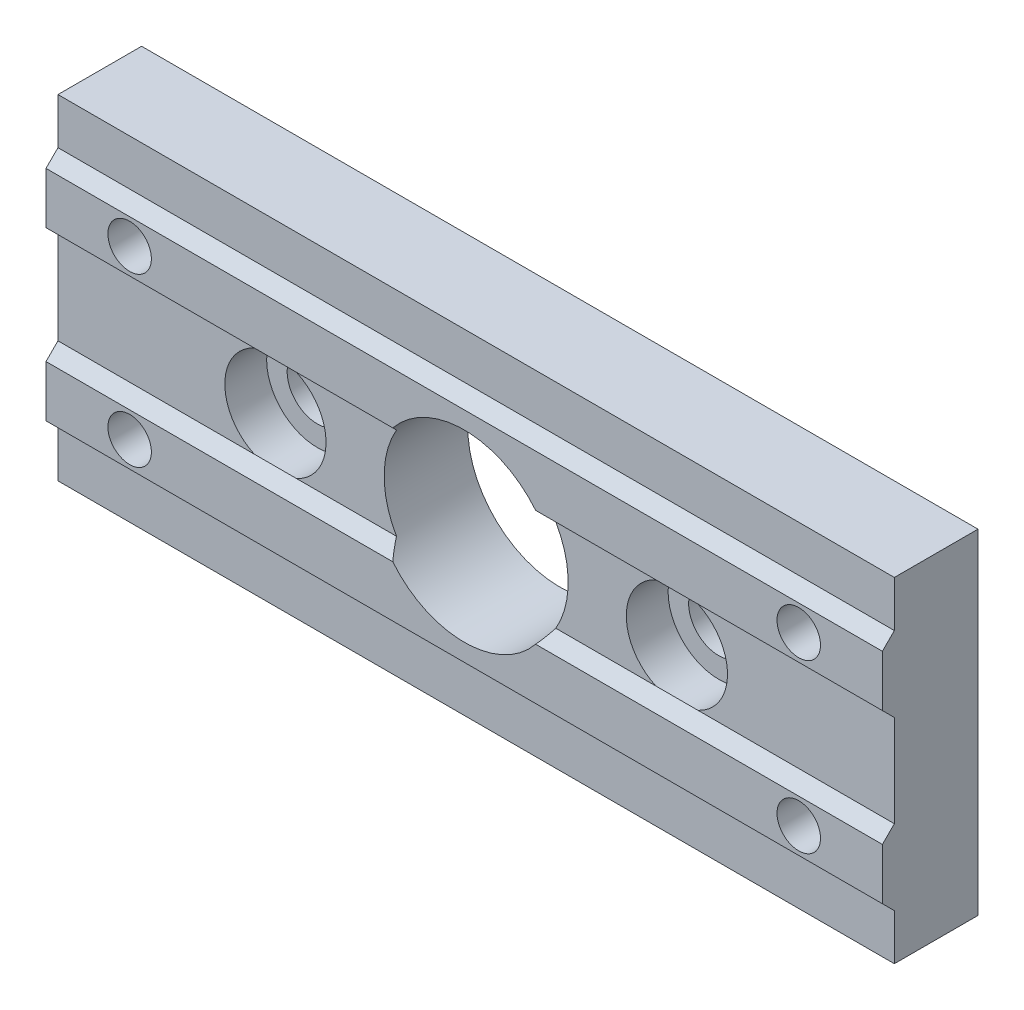
SolidWorks part; units mm, degrees
ref_plane "Płaszczyzna przednia" through (0, 0, 0) normal (0, 0, 1) x (1, 0, 0)
ref_plane "Płaszczyzna górna" through (0, 0, 0) normal (0, 1, 0) x (1, 0, 0)
ref_plane "Płaszczyzna prawa" through (0, 0, 0) normal (1, 0, 0) x (0, 0, -1)
sketch "Sketch1" plane through (0, 0, 0) normal (0, 0, 1) x (1, 0, 0)
  line L0 (-50, 10) -> (50, 10) construction
  line L1 (-50, -20) -> (50, -20)
  line L2 (-50, -20) -> (-50, 20)
  line L3 (-50, 20) -> (50, 20)
  line L4 (50, -20) -> (50, 20)
  line L5 (-50, -20) -> (50, 20) construction
  line L6 (-50, 20) -> (50, -20) construction
  line L7 (-50, -10) -> (50, -10) construction
  line L8 (-40, 20) -> (-40, -20) construction
  line L9 (40, 20) -> (40, -20) construction
  line L10 (-50, 0) -> (50, 0) construction
  circle A0 centre (0, 0) radius 11
  circle A1 centre (-40, 10) radius 2.6
  circle A2 centre (-40, -10) radius 2.6
  circle A3 centre (40, 10) radius 2.6
  circle A4 centre (40, -10) radius 2.6
  circle A5 centre (-24, 0) radius 3.6
  circle A6 centre (24, 0) radius 3.6
  point P0 (0, 0)
  dimension "D7" = 22
  dimension "D8" = 5.2
  dimension "D9" = 7.2
  dimension "D1" = 100
  dimension "D2" = 40
  dimension "D3" = 10
  dimension "D4" = 10
  dimension "D5" = 10
  dimension "D6" = 10
  dimension "D10" = 48
  dimension "D11" = 24
extrude "Boss-Extrude1" add sketch "Sketch1" along normal blind 10
sketch "Sketch2" plane through (0, 0, 0) normal (0, 0, 1) x (1, 0, 0)
  circle A0 centre (24, 0) radius 6.05
  circle A1 centre (-24, 0) radius 6.05
  dimension "D1" = 12.1
  dimension "D2" = 12.1
extrude "Cut-Extrude1" cut sketch "Sketch2" against normal blind 5 from surface starting at face at (0, 0, 10)
sketch "Sketch3" plane through (0, 0, 0) normal (0, 0, 1) x (1, 0, 0)
  circle A0 centre (40, 10) radius 4.5
  circle A1 centre (40, -10) radius 4.5
  circle A2 centre (-40, 10) radius 4.5
  circle A3 centre (-40, -10) radius 4.5
  dimension "D1" = 9
extrude "Cut-Extrude2" cut sketch "Sketch3" along normal blind 5
sketch "Sketch4" plane through (0, 0, 0) normal (1, 0, 0) x (0, 0, -1)
  line L0 (-10, 10) -> (0, 10) construction
  line L1 (-10, -10) -> (0, -10) construction
  line L2 (-10, 20) -> (-10, -20) construction
  line L3 (0, 20) -> (0, -20) construction
  line L6 (-10, 20) -> (0, 20) construction
  line L7 (-10, -20) -> (0, -20) construction
  line L8 (-10, 5.5) -> (-11.43, 5.5)
  line L10 (-10, -14.5) -> (-10, -5.5)
  line L13 (-11.43, 5.5) -> (-11.43, 14.5)
  line L14 (-10, -5.5) -> (-11.43, -5.5)
  line L16 (-10, 5.5) -> (-10, 14.5)
  line L17 (-10, 14.5) -> (-11.43, 14.5)
  line L19 (-11.43, -5.5) -> (-11.43, -14.5)
  line L20 (-11.43, -14.5) -> (-10, -14.5)
  point P10 (0, 0)
  point P24 (0, 0)
  dimension "D1" = 10
  dimension "D2" = 10
  dimension "D3" = 9
  dimension "D4" = 9
  dimension "D5" = 1.43
  dimension "D6" = 1.43
  dimension "D7" = 4.5
extrude "Boss-Extrude3" add sketch "Sketch4" along normal up to surface (50 mm away) from surface up to face at (50, 0, 5) starting at face at (-50, 0, 5)
chamfer "Chamfer1" distance 1.43 angle 45 4 edges at (0, -14.5, 11.43) (0, -5.5, 11.43) (0, 5.5, 11.43) (0, 14.5, 11.43)
sketch "Sketch5" plane through (0, 0, 0) normal (0, 0, 1) x (1, 0, 0)
  circle A0 centre (0, 0) radius 11
  circle A1 centre (-40, 10) radius 2.6
  circle A2 centre (-40, -10) radius 2.6
  circle A3 centre (40, -10) radius 2.6
  circle A4 centre (40, 10) radius 2.6
  dimension "D1" = 22
  dimension "D2" = 5.2
extrude "Cut-Extrude4" cut sketch "Sketch5" along normal through all both and the other way through all from surface starting at face at (44.5, -10, 0)
